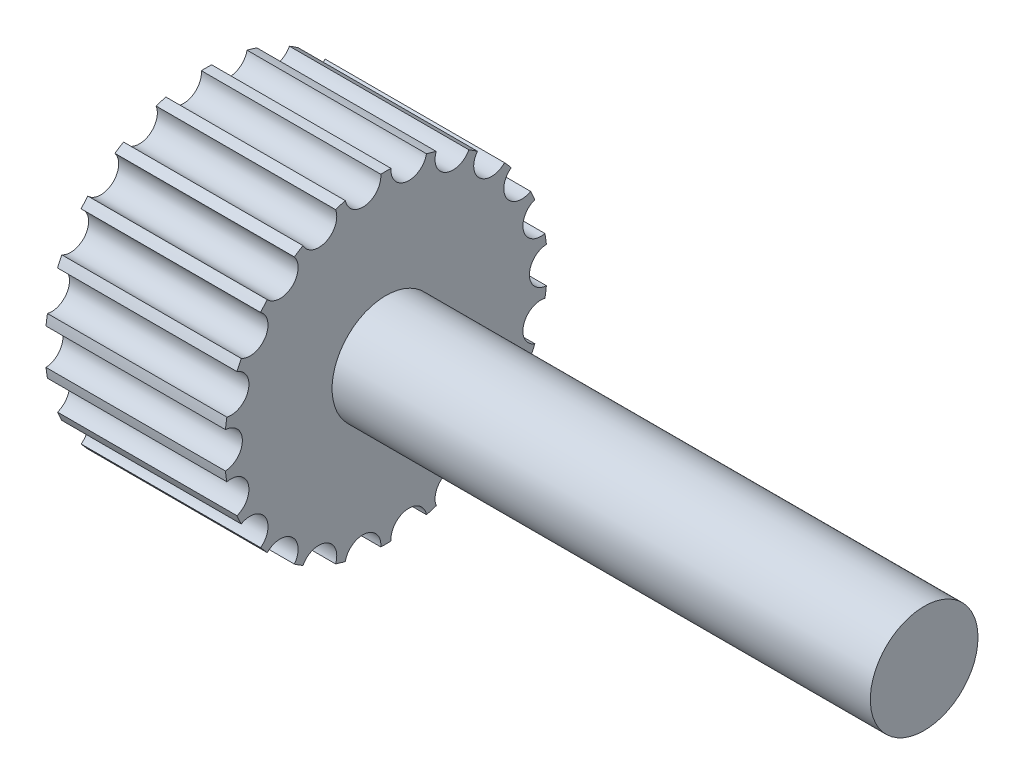
SolidWorks part; units mm, degrees
material "Brass"
ref_plane "Front Plane" through (0, 0, 0) normal (0, 0, 1) x (1, 0, 0)
ref_plane "Top Plane" through (0, 0, 0) normal (0, 1, 0) x (1, 0, 0)
ref_plane "Right Plane" through (0, 0, 0) normal (1, 0, 0) x (0, 0, -1)
sketch "Sketch1" plane through (0, 0, 0) normal (1, 0, 0) x (0, 0, -1)
  circle A0 centre (0, 0) radius 4.5
  dimension "D1" = 9
extrude "Boss-Extrude1" add sketch "Sketch1" along normal blind 5
sketch "Sketch2" plane through (0, 0, 0) normal (1, 0, 0) x (0, 0, -1)
  circle A0 centre (0, 0) radius 1.5
  dimension "D1" = 3
extrude "Boss-Extrude2" add sketch "Sketch2" along normal blind 20
cosmetic thread "Cosmetic Thread1" parameters "D1"=15, "D2"=0
sketch "Sketch3" plane through (0, 0, 0) normal (1, 0, 0) x (0, 0, -1)
  circle A0 centre (4.5, 0) radius 0.5
  dimension "D1" = 1
extrude "Cut-Extrude2" cut sketch "Sketch3" against normal blind 5 and the other way blind 5
ref_axis "Axis1" through (-1, 0, 0) along (1, 0, 0)
pattern_circular "CirPattern1" count 22 over 360 about axis through (-1, 0, 0) along (1, 0, 0) of "Cut-Extrude2"
